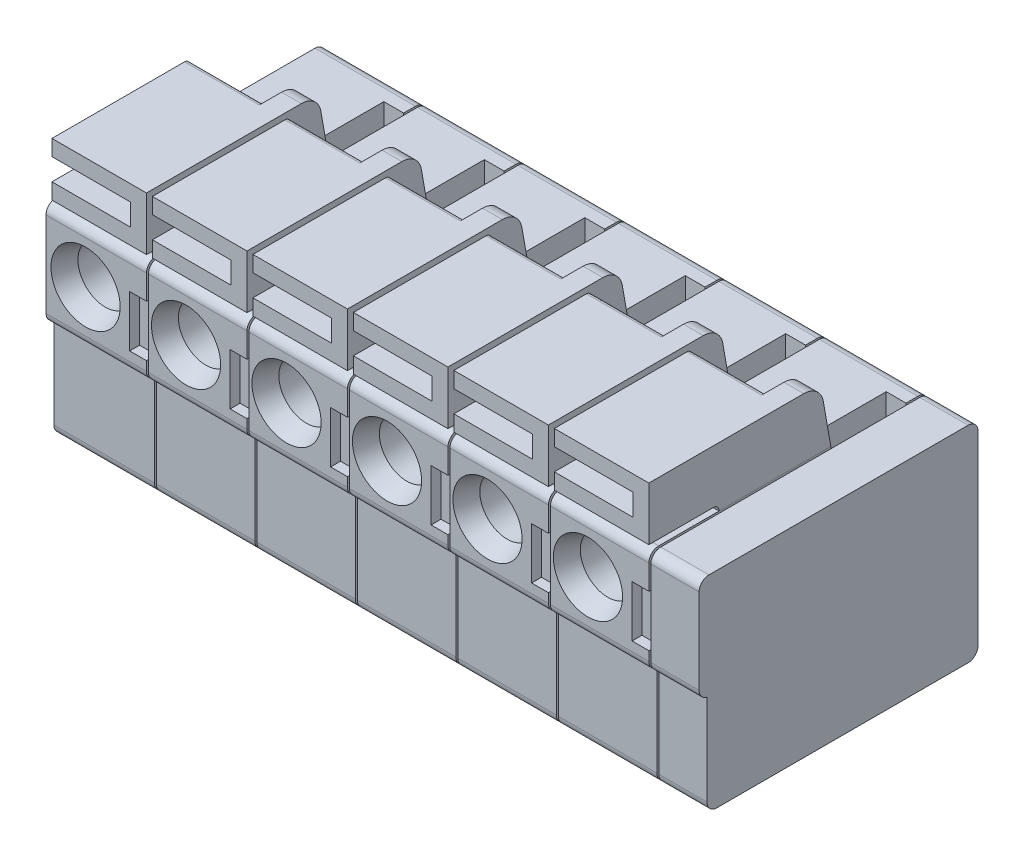
SolidWorks part; units mm, degrees
ref_plane "Спереди" through (0, 0, 0) normal (0, 0, 1) x (1, 0, 0)
ref_plane "Сверху" through (0, 0, 0) normal (0, 1, 0) x (1, 0, 0)
ref_plane "Справа" through (0, 0, 0) normal (1, 0, 0) x (0, 0, -1)
sketch "Эскиз1" plane through (0, 0, 0) normal (1, 0, 0) x (0, 0, -1)
  line L0 (54.1667, 191) -> (270.8333, 191) construction
  line L1 (0, 0) -> (14.1, 0)
  line L2 (0, 0) -> (0, 13.4)
  line L3 (0, 13.4) -> (14.1, 13.4)
  line L4 (14.1, 0) -> (14.1, 13.4)
  line L5 (0, 10.4) -> (14.1, 10.4)
  line L7 (0.4, 5.1) -> (0, 5.1)
  line L8 (0.4, 5.1) -> (0.4, 0)
  line L9 (0.4, 0) -> (0, 0)
  line L10 (0, 5.1) -> (0, 0)
  dimension "D1" = 14.1
  dimension "D2" = 13.4
  dimension "D3" = 10.4
  dimension "D4" = 0.4
  dimension "D5" = 5.1
extrude "Бобышка-Вытянуть1" add sketch "Эскиз1" along normal blind 33.02 contours L7 L8 L1 L4 L5 L2
fillet "Скругление1" radius 0.5 5 edges at (16.51, 10.4, -14.1) (16.51, 0, -14.1) (16.51, 0, -0.4) (16.51, 5.1, 0) (16.51, 10.4, 0)
sketch "Эскиз2" plane through (0, 0, 0) normal (1, 0, 0) x (0, 0, -1)
  line L0 (0, 0) -> (14.1, 0) construction
  line L1 (4.23, 0) -> (5.23, 0)
  line L2 (4.23, 0) -> (4.23, -3.5)
  line L3 (4.23, -3.5) -> (5.23, -3.5)
  line L4 (5.23, 0) -> (5.23, -3.5)
  line L5 (14.1, 0) -> (14.1, 13.4) construction
  line L6 (11.85, 0) -> (12.85, 0)
  line L7 (11.85, 0) -> (11.85, -3.5)
  line L8 (11.85, -3.5) -> (12.85, -3.5)
  line L9 (12.85, 0) -> (12.85, -3.5)
  line L10 (4.23, -2.5) -> (4.4979, -3.5)
  line L11 (4.23, -2.5) -> (12.85, -2.5) construction
  line L12 (5.23, -2.5) -> (4.9621, -3.5)
  line L14 (11.85, -2.5) -> (12.1179, -3.5)
  line L16 (12.85, -2.5) -> (12.5821, -3.5)
  point P10 (4.73, -3.5)
  point P11 (12.35, -3.5)
  dimension "D1" = 1
  dimension "D2" = 1
  dimension "D3" = 3.5
  dimension "D4" = 3.5
  dimension "D5" = 1.75
  dimension "D6" = 7.62
  dimension "D7" = 1
  dimension "D8" = 15
  dimension "D9" = 15
extrude "Бобышка-Вытянуть2" add sketch "Эскиз2" along normal up to surface (33.02 mm away) separate body contours L7 L11 L9 L6 | L11 L14 L8 L16 | L2 L11 L4 L1 | L11 L10 L3 L12 up to face at (33.02, 5.2219, -5.7513)
sketch "Эскиз3" plane through (0, 0, 0) normal (1, 0, 0) x (0, 0, -1)
  line L0 (3.55, 10.4) -> (3.55, 10.41)
  line L1 (0, 10.4) -> (14.1, 10.4) construction
  line L2 (3.26, 10.7) -> (0, 10.7)
  line L3 (0, 0) -> (0, 13.4) construction
  line L4 (0, 10.7) -> (0, 13.4)
  line L5 (0, 13.4) -> (7.8319, 13.4)
  line L6 (0, 13.4) -> (14.1, 13.4) construction
  line L7 (8.8167, 12.5736) -> (9.2, 10.4)
  line L8 (3.55, 10.4) -> (9.2, 10.4)
  arc A0 (3.55, 10.41) -> (3.26, 10.7) centre (3.26, 10.41) ccw
  arc A1 (7.8319, 13.4) -> (8.8167, 12.5736) centre (7.8319, 12.4) cw
  point P18 (8.671, 13.4)
  dimension "D5" = 0.29
  dimension "D6" = 1
  dimension "D1" = 9.2
  dimension "D2" = 80
  dimension "D3" = 0.3
  dimension "D4" = 3.55
extrude "Бобышка-Вытянуть3" add sketch "Эскиз3" along normal up to surface (33.02 mm away) separate body up to face at (33.02, 5.2219, -5.7513)
sketch "Эскиз4" plane through (0, 0, 0) normal (0, 0, 1) x (1, 0, 0)
  line L0 (106.6667, 191.5) -> (533.3333, 191.5) construction
  line L1 (33.02, -3.5) -> (0, -3.5) construction
  line L2 (0, 0) -> (2.29, 0)
  line L3 (0, 0) -> (0, -3.5)
  line L4 (0, -3.5) -> (2.29, -3.5)
  line L5 (2.29, 0) -> (2.29, -3.5)
  line L6 (33.02, 0) -> (0, 0) construction
  line L7 (2.79, 0) -> (7.37, 0)
  line L8 (2.79, 0) -> (2.79, -3.5)
  line L9 (2.79, -3.5) -> (7.37, -3.5)
  line L10 (7.37, 0) -> (7.37, -3.5)
  line L11 (7.87, 0) -> (12.45, 0)
  line L12 (7.87, 0) -> (7.87, -3.5)
  line L13 (7.87, -3.5) -> (12.45, -3.5)
  line L14 (12.45, 0) -> (12.45, -3.5)
  line L15 (33.02, -2.5) -> (33.02, -3.5) construction
  line L16 (12.95, 0) -> (17.53, 0)
  line L17 (12.95, 0) -> (12.95, -3.5)
  line L18 (12.95, -3.5) -> (17.53, -3.5)
  line L19 (17.53, 0) -> (17.53, -3.5)
  line L20 (18.03, 0) -> (22.61, 0)
  line L21 (18.03, 0) -> (18.03, -3.5)
  line L22 (18.03, -3.5) -> (22.61, -3.5)
  line L23 (22.61, 0) -> (22.61, -3.5)
  line L24 (23.11, 0) -> (27.69, 0)
  line L25 (23.11, 0) -> (23.11, -3.5)
  line L26 (23.11, -3.5) -> (27.69, -3.5)
  line L27 (27.69, 0) -> (27.69, -3.5)
  line L28 (28.19, 0) -> (33.02, 0)
  line L29 (28.19, 0) -> (28.19, -3.5)
  line L30 (28.19, -3.5) -> (33.02, -3.5)
  line L31 (33.02, 0) -> (33.02, -3.5)
  line L32 (33.02, 13.4) -> (0, 13.4) construction
  line L33 (0, 10.4) -> (0.3, 10.4)
  line L34 (0, 10.4) -> (0, 13.4)
  line L35 (0, 13.4) -> (0.3, 13.4)
  line L36 (0.3, 10.4) -> (0.3, 13.4)
  line L38 (5.08, 10.4) -> (5.38, 10.4)
  line L39 (5.08, 10.4) -> (5.08, 13.4)
  line L40 (5.08, 13.4) -> (5.38, 13.4)
  line L41 (5.38, 10.4) -> (5.38, 13.4)
  line L42 (33.02, 10.4) -> (0, 10.4) construction
  line L43 (10.16, 10.4) -> (10.46, 10.4)
  line L44 (10.16, 10.4) -> (10.16, 13.4)
  line L45 (10.16, 13.4) -> (10.46, 13.4)
  line L46 (10.46, 10.4) -> (10.46, 13.4)
  line L47 (15.24, 10.4) -> (15.54, 10.4)
  line L48 (15.24, 10.4) -> (15.24, 13.4)
  line L49 (15.24, 13.4) -> (15.54, 13.4)
  line L50 (15.54, 10.4) -> (15.54, 13.4)
  line L51 (20.32, 10.4) -> (20.62, 10.4)
  line L52 (20.32, 10.4) -> (20.32, 13.4)
  line L53 (20.32, 13.4) -> (20.62, 13.4)
  line L54 (20.62, 10.4) -> (20.62, 13.4)
  line L55 (25.4, 10.4) -> (25.7, 10.4)
  line L56 (25.4, 10.4) -> (25.4, 13.4)
  line L57 (25.4, 13.4) -> (25.7, 13.4)
  line L58 (25.7, 10.4) -> (25.7, 13.4)
  line L59 (30.48, 10.4) -> (33.02, 10.4)
  line L60 (30.48, 10.4) -> (30.48, 13.4)
  line L61 (30.48, 13.4) -> (33.02, 13.4)
  line L62 (33.02, 10.4) -> (33.02, 13.4)
  dimension "D1" = 0.5
  dimension "D2" = 0.5
  dimension "D3" = 0.5
  dimension "D4" = 0.5
  dimension "D5" = 0.5
  dimension "D6" = 0.5
  dimension "D7" = 2.29
  dimension "D8" = 5.08
  dimension "D9" = 0.3
  dimension "D10" = 5.08
  dimension "D11" = 5.08
  dimension "D12" = 5.08
  dimension "D13" = 5.08
  dimension "D14" = 5.08
  dimension "D15" = 5.08
extrude "Вырез-Вытянуть1" cut sketch "Эскиз4" against normal through all
sketch "Эскиз5" plane through (0, 0, 0) normal (0, 0, 1) x (1, 0, 0)
  line L0 (0, 7.7449) -> (33.02, 7.7449) construction
  line L1 (0, 0) -> (0, 13.4) construction
  line L2 (33.02, 5.5899) -> (33.02, 9.9) construction
  line L3 (5.08, 10.41) -> (0.3, 10.41) construction
  line L4 (4.23, 8.66) -> (5.08, 8.66)
  line L5 (4.23, 8.66) -> (4.23, 6.06)
  line L6 (4.23, 6.06) -> (5.08, 6.06)
  line L7 (5.08, 8.66) -> (5.08, 6.06)
  line L8 (9.31, 8.66) -> (10.16, 8.66)
  line L9 (9.31, 8.66) -> (9.31, 6.06)
  line L10 (9.31, 6.06) -> (10.16, 6.06)
  line L11 (10.16, 8.66) -> (10.16, 6.06)
  line L12 (14.39, 8.66) -> (15.24, 8.66)
  line L13 (14.39, 8.66) -> (14.39, 6.06)
  line L14 (14.39, 6.06) -> (15.24, 6.06)
  line L15 (15.24, 8.66) -> (15.24, 6.06)
  line L16 (19.47, 8.66) -> (20.32, 8.66)
  line L17 (19.47, 8.66) -> (19.47, 6.06)
  line L18 (19.47, 6.06) -> (20.32, 6.06)
  line L19 (20.32, 8.66) -> (20.32, 6.06)
  line L20 (24.55, 8.66) -> (25.4, 8.66)
  line L21 (24.55, 8.66) -> (24.55, 6.06)
  line L22 (24.55, 6.06) -> (25.4, 6.06)
  line L23 (25.4, 8.66) -> (25.4, 6.06)
  line L24 (29.63, 8.66) -> (30.48, 8.66)
  line L25 (29.63, 8.66) -> (29.63, 6.06)
  line L26 (29.63, 6.06) -> (30.48, 6.06)
  line L27 (30.48, 8.66) -> (30.48, 6.06)
  dimension "D1" = 5.08
  dimension "D2" = 0.85
  dimension "D3" = 1.75
  dimension "D4" = 2.6
  dimension "D5" = 5.08
  dimension "D6" = 5.08
  dimension "D7" = 5.08
  dimension "D8" = 5.08
  dimension "D9" = 5.08
extrude "Вырез-Вытянуть2" cut sketch "Эскиз5" against normal blind 0.5
sketch "Эскиз6" plane through (0, 0, 0) normal (0, 0, 1) x (1, 0, 0)
  line L0 (0.3, 10.4) -> (0.3, 13.4) construction
  line L1 (0.3, 12.6) -> (4.28, 12.6)
  line L2 (0.3, 12.6) -> (0.3, 11.5)
  line L3 (0.3, 11.5) -> (4.28, 11.5)
  line L4 (4.28, 12.6) -> (4.28, 11.5)
  line L5 (10.46, 10.4) -> (10.46, 13.4) construction
  line L6 (5.38, 12.6) -> (9.36, 12.6)
  line L7 (5.38, 12.6) -> (5.38, 11.5)
  line L8 (5.38, 11.5) -> (9.36, 11.5)
  line L9 (9.36, 12.6) -> (9.36, 11.5)
  line L10 (10.46, 12.6) -> (14.44, 12.6)
  line L11 (10.46, 12.6) -> (10.46, 11.5)
  line L12 (10.46, 11.5) -> (14.44, 11.5)
  line L13 (14.44, 12.6) -> (14.44, 11.5)
  line L14 (15.54, 10.4) -> (15.54, 13.4) construction
  line L15 (15.54, 12.6) -> (19.52, 12.6)
  line L16 (15.54, 12.6) -> (15.54, 11.5)
  line L17 (15.54, 11.5) -> (19.52, 11.5)
  line L18 (19.52, 12.6) -> (19.52, 11.5)
  line L19 (20.62, 10.4) -> (20.62, 13.4) construction
  line L20 (20.62, 12.6) -> (24.6, 12.6)
  line L21 (20.62, 12.6) -> (20.62, 11.5)
  line L22 (20.62, 11.5) -> (24.6, 11.5)
  line L23 (24.6, 12.6) -> (24.6, 11.5)
  line L24 (25.7, 10.4) -> (25.7, 13.4) construction
  line L25 (25.7, 12.6) -> (29.68, 12.6)
  line L26 (25.7, 12.6) -> (25.7, 11.5)
  line L27 (25.7, 11.5) -> (29.68, 11.5)
  line L28 (29.68, 12.6) -> (29.68, 11.5)
  line L29 (5.08, 13.4) -> (0.3, 13.4) construction
  line L30 (5.08, 10.7) -> (0.3, 10.7) construction
  line L31 (5.08, 10.4) -> (5.08, 13.4) construction
  line L32 (5.38, 10.4) -> (5.38, 13.4) construction
  dimension "D1" = 0.8
  dimension "D2" = 0.8
  dimension "D3" = 0.8
extrude "Вырез-Вытянуть3" cut sketch "Эскиз6" against normal blind 1.5
sketch "Эскиз7" plane through (0, 0, 0) normal (0, 0, 1) x (1, 0, 0)
  line L0 (33.02, 7.7449) -> (0, 7.7449) construction
  line L1 (33.02, 5.5899) -> (33.02, 9.9) construction
  line L2 (0, 0) -> (0, 13.4) construction
  circle A0 centre (2, 7.7449) radius 1.75
  circle A1 centre (7.08, 7.7449) radius 1.75
  circle A2 centre (12.16, 7.7449) radius 1.75
  circle A3 centre (17.24, 7.7449) radius 1.75
  circle A4 centre (22.32, 7.7449) radius 1.75
  circle A5 centre (27.4, 7.7449) radius 1.75
  dimension "D1" = 3.5
  dimension "D2" = 5.08
  dimension "D3" = 5.08
  dimension "D4" = 5.08
  dimension "D5" = 5.08
  dimension "D6" = 5.08
  dimension "D7" = 2
extrude "Вырез-Вытянуть4" cut sketch "Эскиз7" against normal blind 1 draft 20
sketch "Эскиз8" plane through (0, 0, -1) normal (0, 0, 1) x (1, 0, 0)
  circle A2 centre (27.4, 7.7449) radius 1.386
  circle A3 centre (27.4, 7.7449) radius 1.386
  circle A5 centre (22.32, 7.7449) radius 1.386
  circle A6 centre (22.32, 7.7449) radius 1.386
  circle A8 centre (17.24, 7.7449) radius 1.386
  circle A9 centre (17.24, 7.7449) radius 1.386
  circle A11 centre (12.16, 7.7449) radius 1.386
  circle A12 centre (12.16, 7.7449) radius 1.386
  circle A14 centre (7.08, 7.7449) radius 1.386
  circle A15 centre (7.08, 7.7449) radius 1.386
  circle A17 centre (2, 7.7449) radius 1.386
  circle A18 centre (2, 7.7449) radius 1.386
  dimension "D1" = 0
  dimension "D2" = 0
  dimension "D3" = 0
  dimension "D4" = 0
  dimension "D5" = 0
  dimension "D6" = 0
extrude "Вырез-Вытянуть5" cut sketch "Эскиз8" against normal blind 8
sketch "Эскиз9" plane through (0.3, 0, 0) normal (-1, 0, 0) x (0, 0, 1)
  line L0 (38.7333, 189.5) -> (250.0667, 189.5) construction
  line L1 (-1.4, 10.4) -> (-6.8115, 12.9234)
  line L2 (-0.5, 10.4) -> (-13.6, 10.4) construction
  line L3 (-7.8319, 13.4) -> (0, 13.4) construction
  line L4 (-6.7058, 13.4) -> (0, 13.4)
  line L5 (0, 13.4) -> (0, 14.4)
  line L6 (0, 14.4) -> (-13.6, 14.4)
  line L7 (-13.6, 14.4) -> (-13.6, 10.4)
  arc A0 (-6.8115, 12.9234) -> (-6.7058, 13.4) centre (-6.7058, 13.15) cw
  point P20 (-7.8335, 13.4)
  dimension "D4" = 0.25
  dimension "D1" = 4
  dimension "D2" = 25
  dimension "D3" = 1.4
extrude "Вырез-Вытянуть6" cut sketch "Эскиз9" against normal blind 3.78 and the other way through all
sketch "Эскиз10" plane through (5.38, 0, 0) normal (-1, 0, 0) x (0, 0, 1)
  line L12 (-8.8167, 12.5736) -> (-9.2, 10.4)
  line L13 (-9.2, 10.4) -> (-3.55, 10.4)
  line L14 (-3.55, 10.4) -> (-3.55, 10.41)
  line L15 (-3.26, 10.7) -> (-2.0434, 10.7)
  line L16 (-2.0434, 10.7) -> (-6.8115, 12.9234)
  line L17 (-6.7058, 13.4) -> (-7.8319, 13.4)
  line L18 (-8.8167, 12.5736) -> (-9.2, 10.4)
  line L19 (-9.2, 10.4) -> (-3.55, 10.4)
  line L20 (-3.55, 10.4) -> (-3.55, 10.41)
  line L21 (-3.26, 10.7) -> (-2.0434, 10.7)
  line L22 (-2.0434, 10.7) -> (-6.8115, 12.9234)
  line L23 (-6.7058, 13.4) -> (-7.8319, 13.4)
  arc A6 (-3.26, 10.7) -> (-3.55, 10.41) centre (-3.26, 10.41) ccw
  arc A7 (-6.7058, 13.4) -> (-6.8115, 12.9234) centre (-6.7058, 13.15) ccw
  arc A8 (-7.8319, 13.4) -> (-8.8167, 12.5736) centre (-7.8319, 12.4) ccw
  arc A9 (-3.26, 10.7) -> (-3.55, 10.41) centre (-3.26, 10.41) ccw
  arc A10 (-6.7058, 13.4) -> (-6.8115, 12.9234) centre (-6.7058, 13.15) ccw
  arc A11 (-7.8319, 13.4) -> (-8.8167, 12.5736) centre (-7.8319, 12.4) ccw
  dimension "D1" = 0
extrude "Вырез-Вытянуть7" cut sketch "Эскиз10" against normal blind 3.78
sketch "Эскиз13" plane through (10.46, 0, 0) normal (-1, 0, 0) x (0, 0, 1)
  line L12 (-8.8167, 12.5736) -> (-9.2, 10.4)
  line L13 (-9.2, 10.4) -> (-3.55, 10.4)
  line L14 (-3.55, 10.4) -> (-3.55, 10.41)
  line L15 (-3.26, 10.7) -> (-2.0434, 10.7)
  line L16 (-2.0434, 10.7) -> (-6.8115, 12.9234)
  line L17 (-6.7058, 13.4) -> (-7.8319, 13.4)
  line L18 (-8.8167, 12.5736) -> (-9.2, 10.4)
  line L19 (-9.2, 10.4) -> (-3.55, 10.4)
  line L20 (-3.55, 10.4) -> (-3.55, 10.41)
  line L21 (-3.26, 10.7) -> (-2.0434, 10.7)
  line L22 (-2.0434, 10.7) -> (-6.8115, 12.9234)
  line L23 (-6.7058, 13.4) -> (-7.8319, 13.4)
  arc A6 (-7.8319, 13.4) -> (-8.8167, 12.5736) centre (-7.8319, 12.4) ccw
  arc A7 (-3.26, 10.7) -> (-3.55, 10.41) centre (-3.26, 10.41) ccw
  arc A8 (-6.7058, 13.4) -> (-6.8115, 12.9234) centre (-6.7058, 13.15) ccw
  arc A9 (-7.8319, 13.4) -> (-8.8167, 12.5736) centre (-7.8319, 12.4) ccw
  arc A10 (-3.26, 10.7) -> (-3.55, 10.41) centre (-3.26, 10.41) ccw
  arc A11 (-6.7058, 13.4) -> (-6.8115, 12.9234) centre (-6.7058, 13.15) ccw
  dimension "D1" = 0
extrude "Вырез-Вытянуть8" cut sketch "Эскиз13" against normal blind 3.78
sketch "Эскиз14" plane through (15.54, 0, 0) normal (-1, 0, 0) x (0, 0, 1)
  line L12 (-8.8167, 12.5736) -> (-9.2, 10.4)
  line L13 (-9.2, 10.4) -> (-3.55, 10.4)
  line L14 (-3.55, 10.4) -> (-3.55, 10.41)
  line L15 (-3.26, 10.7) -> (-2.0434, 10.7)
  line L16 (-2.0434, 10.7) -> (-6.8115, 12.9234)
  line L17 (-6.7058, 13.4) -> (-7.8319, 13.4)
  line L18 (-8.8167, 12.5736) -> (-9.2, 10.4)
  line L19 (-9.2, 10.4) -> (-3.55, 10.4)
  line L20 (-3.55, 10.4) -> (-3.55, 10.41)
  line L21 (-3.26, 10.7) -> (-2.0434, 10.7)
  line L22 (-2.0434, 10.7) -> (-6.8115, 12.9234)
  line L23 (-6.7058, 13.4) -> (-7.8319, 13.4)
  arc A6 (-7.8319, 13.4) -> (-8.8167, 12.5736) centre (-7.8319, 12.4) ccw
  arc A7 (-3.26, 10.7) -> (-3.55, 10.41) centre (-3.26, 10.41) ccw
  arc A8 (-6.7058, 13.4) -> (-6.8115, 12.9234) centre (-6.7058, 13.15) ccw
  arc A9 (-7.8319, 13.4) -> (-8.8167, 12.5736) centre (-7.8319, 12.4) ccw
  arc A10 (-3.26, 10.7) -> (-3.55, 10.41) centre (-3.26, 10.41) ccw
  arc A11 (-6.7058, 13.4) -> (-6.8115, 12.9234) centre (-6.7058, 13.15) ccw
  dimension "D1" = 0
extrude "Вырез-Вытянуть9" cut sketch "Эскиз14" against normal blind 3.78
sketch "Эскиз15" plane through (20.62, 0, 0) normal (-1, 0, 0) x (0, 0, 1)
  line L12 (-8.8167, 12.5736) -> (-9.2, 10.4)
  line L13 (-9.2, 10.4) -> (-3.55, 10.4)
  line L14 (-3.55, 10.4) -> (-3.55, 10.41)
  line L15 (-3.26, 10.7) -> (-2.0434, 10.7)
  line L16 (-2.0434, 10.7) -> (-6.8115, 12.9234)
  line L17 (-6.7058, 13.4) -> (-7.8319, 13.4)
  line L18 (-8.8167, 12.5736) -> (-9.2, 10.4)
  line L19 (-9.2, 10.4) -> (-3.55, 10.4)
  line L20 (-3.55, 10.4) -> (-3.55, 10.41)
  line L21 (-3.26, 10.7) -> (-2.0434, 10.7)
  line L22 (-2.0434, 10.7) -> (-6.8115, 12.9234)
  line L23 (-6.7058, 13.4) -> (-7.8319, 13.4)
  arc A6 (-7.8319, 13.4) -> (-8.8167, 12.5736) centre (-7.8319, 12.4) ccw
  arc A7 (-3.26, 10.7) -> (-3.55, 10.41) centre (-3.26, 10.41) ccw
  arc A8 (-6.7058, 13.4) -> (-6.8115, 12.9234) centre (-6.7058, 13.15) ccw
  arc A9 (-7.8319, 13.4) -> (-8.8167, 12.5736) centre (-7.8319, 12.4) ccw
  arc A10 (-3.26, 10.7) -> (-3.55, 10.41) centre (-3.26, 10.41) ccw
  arc A11 (-6.7058, 13.4) -> (-6.8115, 12.9234) centre (-6.7058, 13.15) ccw
  dimension "D1" = 0
extrude "Вырез-Вытянуть10" cut sketch "Эскиз15" against normal blind 3.78
sketch "Эскиз16" plane through (25.7, 0, 0) normal (-1, 0, 0) x (0, 0, 1)
  line L12 (-8.8167, 12.5736) -> (-9.2, 10.4)
  line L13 (-9.2, 10.4) -> (-3.55, 10.4)
  line L14 (-3.55, 10.4) -> (-3.55, 10.41)
  line L15 (-3.26, 10.7) -> (-2.0434, 10.7)
  line L16 (-2.0434, 10.7) -> (-6.8115, 12.9234)
  line L17 (-6.7058, 13.4) -> (-7.8319, 13.4)
  line L18 (-8.8167, 12.5736) -> (-9.2, 10.4)
  line L19 (-9.2, 10.4) -> (-3.55, 10.4)
  line L20 (-3.55, 10.4) -> (-3.55, 10.41)
  line L21 (-3.26, 10.7) -> (-2.0434, 10.7)
  line L22 (-2.0434, 10.7) -> (-6.8115, 12.9234)
  line L23 (-6.7058, 13.4) -> (-7.8319, 13.4)
  arc A6 (-7.8319, 13.4) -> (-8.8167, 12.5736) centre (-7.8319, 12.4) ccw
  arc A7 (-3.26, 10.7) -> (-3.55, 10.41) centre (-3.26, 10.41) ccw
  arc A8 (-6.7058, 13.4) -> (-6.8115, 12.9234) centre (-6.7058, 13.15) ccw
  arc A9 (-7.8319, 13.4) -> (-8.8167, 12.5736) centre (-7.8319, 12.4) ccw
  arc A10 (-3.26, 10.7) -> (-3.55, 10.41) centre (-3.26, 10.41) ccw
  arc A11 (-6.7058, 13.4) -> (-6.8115, 12.9234) centre (-6.7058, 13.15) ccw
  dimension "D1" = 0
extrude "Вырез-Вытянуть11" cut sketch "Эскиз16" against normal blind 3.78
sketch "Эскиз17" plane through (0, 10.4, 0) normal (0, 1, 0) x (1, 0, 0)
  line L0 (106.8333, 159.5) -> (534.1667, 159.5) construction
  line L1 (5.08, 7.8319) -> (5.08, 0) construction
  line L2 (5.08, 9.2) -> (4.08, 9.2)
  line L3 (5.08, 9.2) -> (5.08, 13)
  line L4 (5.08, 13) -> (4.08, 13)
  line L5 (4.08, 9.2) -> (4.08, 13)
  line L6 (10.16, 7.8319) -> (10.16, 0) construction
  line L7 (10.16, 9.2) -> (9.16, 9.2)
  line L8 (10.16, 9.2) -> (10.16, 13)
  line L9 (10.16, 13) -> (9.16, 13)
  line L10 (9.16, 9.2) -> (9.16, 13)
  line L11 (15.24, 7.8319) -> (15.24, 0) construction
  line L12 (15.24, 9.2) -> (14.24, 9.2)
  line L13 (15.24, 9.2) -> (15.24, 13)
  line L14 (15.24, 13) -> (14.24, 13)
  line L15 (14.24, 9.2) -> (14.24, 13)
  line L16 (20.32, 7.8319) -> (20.32, 0) construction
  line L17 (20.32, 9.2) -> (19.32, 9.2)
  line L18 (20.32, 9.2) -> (20.32, 13)
  line L19 (20.32, 13) -> (19.32, 13)
  line L20 (19.32, 9.2) -> (19.32, 13)
  line L21 (25.4, 7.8319) -> (25.4, 0) construction
  line L22 (25.4, 9.2) -> (24.4, 9.2)
  line L23 (25.4, 9.2) -> (25.4, 13)
  line L24 (25.4, 13) -> (24.4, 13)
  line L25 (24.4, 9.2) -> (24.4, 13)
  line L26 (30.48, 7.8319) -> (30.48, 0) construction
  line L27 (30.48, 9.2) -> (29.48, 9.2)
  line L28 (30.48, 9.2) -> (30.48, 13)
  line L29 (30.48, 13) -> (29.48, 13)
  line L30 (29.48, 9.2) -> (29.48, 13)
  line L31 (0, 14.1) -> (33.02, 14.1) construction
  line L32 (9.16, 9.2) -> (9.16, 3.55) construction
  line L33 (10.16, 9.2) -> (9.16, 9.2) construction
  dimension "D1" = 1.1
extrude "Вырез-Вытянуть12" cut sketch "Эскиз17" against normal blind 3.78
sketch "Эскиз18" plane through (0, 0, 0) normal (0, 0, 1) x (1, 0, 0)
  line L0 (33.02, 0) -> (0, 0) construction
  line L1 (5.08, 13.4) -> (5.18, 13.4)
  line L2 (5.08, 13.4) -> (5.08, 0)
  line L3 (5.08, 0) -> (5.18, 0)
  line L4 (5.18, 13.4) -> (5.18, 0)
  line L5 (10.16, 13.4) -> (10.26, 13.4)
  line L6 (10.16, 13.4) -> (10.16, 0)
  line L7 (10.16, 0) -> (10.26, 0)
  line L8 (10.26, 13.4) -> (10.26, 0)
  line L9 (15.24, 13.4) -> (15.34, 13.4)
  line L10 (15.24, 13.4) -> (15.24, 0)
  line L11 (15.24, 0) -> (15.34, 0)
  line L12 (15.34, 13.4) -> (15.34, 0)
  line L13 (20.32, 13.4) -> (20.42, 13.4)
  line L14 (20.32, 13.4) -> (20.32, 0)
  line L15 (20.32, 0) -> (20.42, 0)
  line L16 (20.42, 13.4) -> (20.42, 0)
  line L17 (25.4, 13.4) -> (25.5, 13.4)
  line L18 (25.4, 13.4) -> (25.4, 0)
  line L19 (25.4, 0) -> (25.5, 0)
  line L20 (25.5, 13.4) -> (25.5, 0)
  line L21 (30.48, 13.4) -> (30.58, 13.4)
  line L22 (30.48, 13.4) -> (30.48, 0)
  line L23 (30.48, 0) -> (30.58, 0)
  line L24 (30.58, 13.4) -> (30.58, 0)
  dimension "D1" = 0.1
extrude "Вырез-Вытянуть13" cut sketch "Эскиз18" against normal through all
